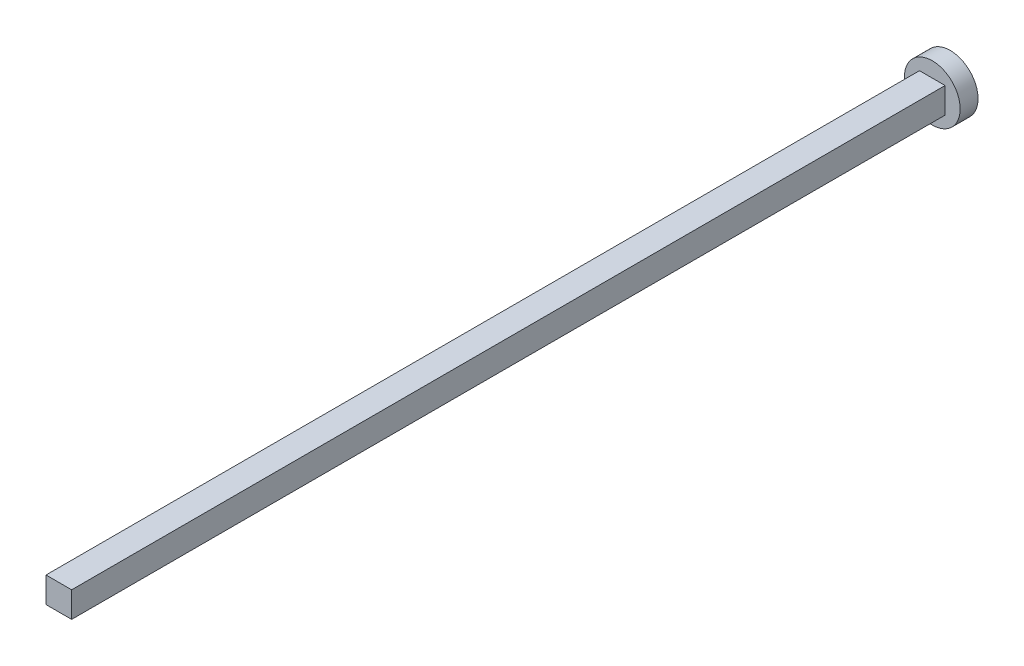
SolidWorks part; units mm, degrees
ref_plane "Front Plane" through (0, 0, 0) normal (0, 0, 1) x (1, 0, 0)
ref_plane "Top Plane" through (0, 0, 0) normal (0, 1, 0) x (1, 0, 0)
ref_plane "Right Plane" through (0, 0, 0) normal (1, 0, 0) x (0, 0, -1)
sketch "Sketch1" plane through (0, 0, 0) normal (0, 0, 1) x (1, 0, 0)
  line L1 (-1.4338, -1.4338) -> (1.4338, -1.4338)
  line L2 (-1.4338, -1.4338) -> (-1.4338, 1.4338)
  line L3 (-1.4338, 1.4338) -> (1.4338, 1.4338)
  line L4 (1.4338, -1.4338) -> (1.4338, 1.4338)
  line L5 (-1.4338, -1.4338) -> (1.4338, 1.4338) construction
  line L6 (-1.4338, 1.4338) -> (1.4338, -1.4338) construction
  point P0 (0, 0)
  dimension "D1" = 2.8676
extrude "Boss-Extrude1" add sketch "Sketch1" along normal blind 97.65
sketch "Sketch2" plane through (0, 0, 0) normal (0, 0, -1) x (-1, 0, 0)
  circle A0 centre (0, 0) radius 3.1162
extrude "Boss-Extrude2" add sketch "Sketch2" along normal blind 2
ref_axis "Axis1" through (0, 0, 105.1) along (0, 0, -1)
